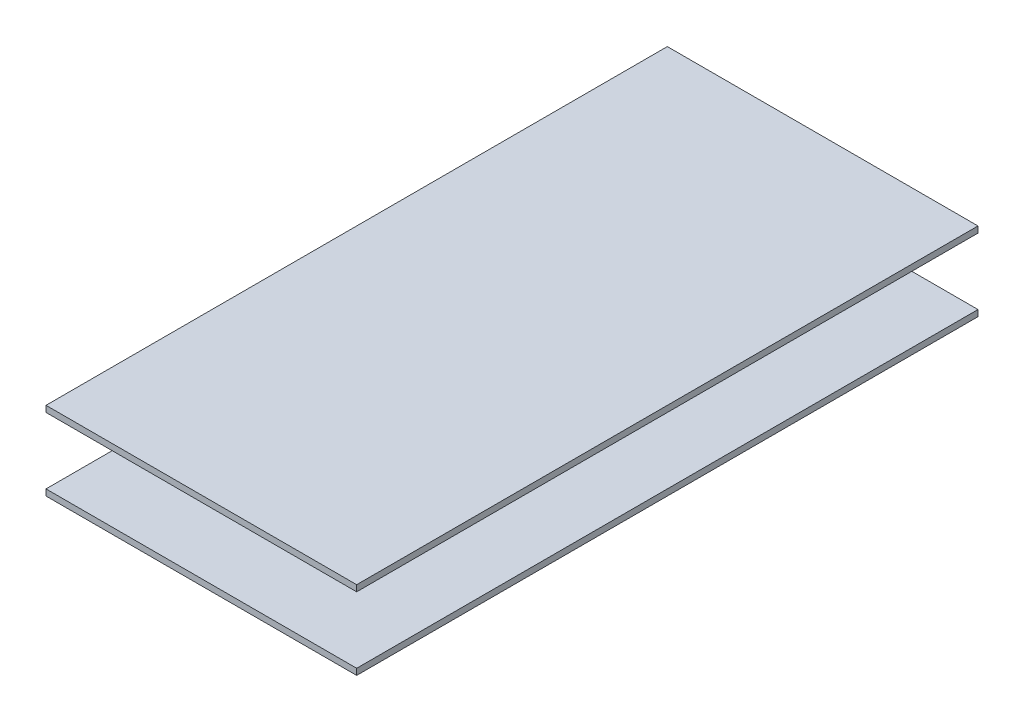
SolidWorks part; units mm, degrees
ref_plane "Front Plane" through (0, 0, 0) normal (0, 0, 1) x (1, 0, 0)
ref_plane "Top Plane" through (0, 0, 0) normal (0, 1, 0) x (1, 0, 0)
ref_plane "Right Plane" through (0, 0, 0) normal (1, 0, 0) x (0, 0, -1)
sketch "Sketch1" plane through (0, 0, 0) normal (0, 0, 1) x (1, 0, 0)
  line L1 (0, 0) -> (12.7, 0)
  line L2 (0, 0) -> (0, 12.7)
  line L3 (0, 12.7) -> (12.7, 12.7)
  line L4 (12.7, 0) -> (12.7, 12.7)
  dimension "D1" = 12.7
extrude "Boss-Extrude1" add sketch "Sketch1" along normal blind 80
sketch "Sketch2" plane through (0, 12.7, 0) normal (0, 1, 0) x (1, 0, 0)
  line L0 (12.7, 0) -> (0, 0) construction
  circle A0 centre (6.6687, -5) radius 2
  circle A1 centre (6.6687, -20) radius 2
  circle A2 centre (6.6687, -60) radius 2
  circle A3 centre (6.6687, -75) radius 2
  dimension "D1" = 4
  dimension "D2" = 5
  dimension "D3" = 15
  dimension "D4" = 40
  dimension "D5" = 15
extrude "Cut-Extrude1" cut sketch "Sketch2" against normal through all
sketch "Sketch4" plane through (0, 0, 0) normal (-1, 0, 0) x (0, 0, 1)
  line L0 (40, 0) -> (40, 12.7) construction
  line L1 (80, 0) -> (0, 0) construction
  line L2 (80, 12.7) -> (0, 12.7) construction
  line L3 (-1.1232, 205.6227) -> (294.8768, 205.6227) construction
  arc A0 (40, 2.7275) -> (40, 9.9725) centre (43.8, 6.35) ccw
  arc A1 (40, 9.9725) -> (40, 2.7275) centre (36.2, 6.35) ccw
  point P13 (40, 6.35)
  dimension "D1" = 10.5
  dimension "D3" = 10.5
  dimension "D4" = 3.8
extrude "Cut-Extrude2" cut sketch "Sketch4" against normal through all
sketch "Sketch5" plane through (0, 0, 0) normal (0, 1, 0) x (1, 0, 0)
  circle A0 centre (6.6687, -20) radius 2 construction
  circle A1 centre (6.6687, -5) radius 2 construction
  circle A2 centre (6.6687, -20) radius 2
  circle A3 centre (6.6687, -5) radius 2
extrude "Boss-Extrude2" add sketch "Sketch5" along normal blind 17
sketch "Sketch6" plane through (0, 12.7, 0) normal (0, 1, 0) x (1, 0, 0)
  circle A0 centre (6.6687, -75) radius 2 construction
  circle A1 centre (6.6687, -60) radius 2 construction
  circle A2 centre (6.6687, -75) radius 2
  circle A3 centre (6.6687, -60) radius 2
extrude "Boss-Extrude3" add sketch "Sketch6" against normal blind 17
sketch "Sketch7" plane through (0, 17, 0) normal (0, 1, 0) x (1, 0, 0)
  line L0 (12.7, 0) -> (0, 0) construction
  line L1 (-43.65, -140) -> (56.35, -140)
  line L2 (-43.65, -140) -> (-43.65, 60)
  line L3 (-43.65, 60) -> (56.35, 60)
  line L4 (56.35, -140) -> (56.35, 60)
  line L6 (0, -80) -> (0, 0) construction
  dimension "D1" = 200
  dimension "D2" = 100
  dimension "D3" = 60
  dimension "D4" = 43.65
extrude "Boss-Extrude4" add sketch "Sketch7" along normal blind 2
sketch "Sketch8" plane through (0, -4.3, 0) normal (0, -1, 0) x (1, 0, 0)
  line L0 (56.35, -60) -> (-43.65, -60) construction
  line L1 (-43.65, -60) -> (-43.65, 140) construction
  line L2 (-43.65, 140) -> (56.35, 140) construction
  line L3 (56.35, -60) -> (-43.65, -60)
  line L4 (-43.65, -60) -> (-43.65, 140)
  line L5 (-43.65, 140) -> (56.35, 140)
  line L6 (56.35, 140) -> (56.35, -60) construction
  line L7 (56.35, 140) -> (56.35, -60)
extrude "Boss-Extrude5" add sketch "Sketch8" along normal blind 2
